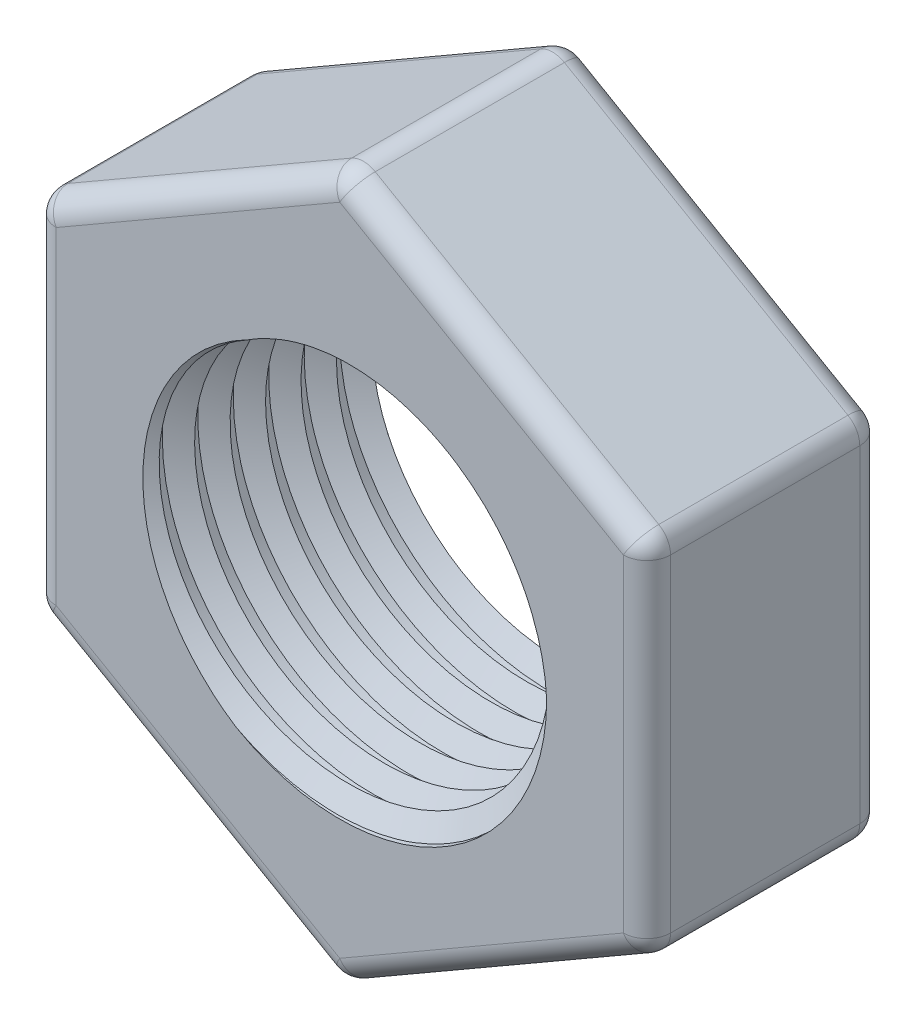
SolidWorks part; units mm, degrees
ref_plane "Front Plane" through (0, 0, 0) normal (0, 0, 1) x (1, 0, 0)
ref_plane "Top Plane" through (0, 0, 0) normal (0, 1, 0) x (1, 0, 0)
ref_plane "Right Plane" through (0, 0, 0) normal (1, 0, 0) x (0, 0, -1)
sketch "Sketch1" plane through (0, 0, 0) normal (0, 0, 1) x (1, 0, 0)
  line L1 (0, -30) -> (25.9808, -15)
  line L2 (25.9808, -15) -> (25.9808, 15)
  line L3 (25.9808, 15) -> (0, 30)
  line L4 (0, 30) -> (-25.9808, 15)
  line L5 (-25.9808, 15) -> (-25.9808, -15)
  line L6 (-25.9808, -15) -> (0, -30)
  circle A0 centre (0, 0) radius 17.5
  circle A1 centre (0, 0) radius 25.9808 construction
  dimension "D1" = 35
  dimension "D2" = 30
extrude "Boss-Extrude1" add sketch "Sketch1" along normal blind 20
sketch "Sketch2" plane through (0, 0, 0) normal (0, 0, 1) x (1, 0, 0)
  circle A0 centre (0, 0) radius 17.5
curve "Helix/Spiral1" pitch 3 height 60 radius 17.5 left hand yes centre (0, 0, 0) axis (0, 0, 1) start towards (1, 0, 0)
sketch "Sketch3" plane through (0, 0, 0) normal (0, 1, 0) x (1, 0, 0)
  line L0 (17.5, 1) -> (15.7679, 0)
  line L1 (15.7679, 0) -> (17.5, -1)
  line L2 (17.5, -1) -> (17.5, 1)
  point P3 (17.5, 0)
  dimension "D1" = 2
  dimension "D2" = 2
  dimension "D3" = 2
  dimension "D4" = 0
sweep "Sweep1" add profiles "Sketch3" path "Helix/Spiral1"
sketch "Sketch4" plane through (0, 0, 0) normal (0, 1, 0) x (1, 0, 0)
  line L1 (-25.9808, -20) -> (25.9808, -20)
  line L2 (-25.9808, -20) -> (-25.9808, -63.133)
  line L3 (-25.9808, -63.133) -> (25.9808, -63.133)
  line L4 (25.9808, -20) -> (25.9808, -63.133)
  line L5 (-25.9808, -20) -> (25.9808, -63.133) construction
  line L6 (-25.9808, -63.133) -> (25.9808, -20) construction
  point P4 (0, -41.5665)
extrude "Cut-Extrude1" cut sketch "Sketch4" against normal mid plane 80
sketch "Sketch5" plane through (0, 0, 0) normal (0, 1, 0) x (1, 0, 0)
  line L1 (25.9808, 0) -> (-25.9808, 0)
  line L2 (25.9808, 0) -> (25.9808, 6.7971)
  line L3 (25.9808, 6.7971) -> (-25.9808, 6.7971)
  line L4 (-25.9808, 0) -> (-25.9808, 6.7971)
  line L5 (25.9808, 0) -> (-25.9808, 6.7971) construction
  line L6 (25.9808, 6.7971) -> (-25.9808, 0) construction
  point P5 (0, 3.3985)
extrude "Cut-Extrude2" cut sketch "Sketch5" against normal mid plane 80
fillet "Fillet1" radius 2 18 edges at (25.9808, 0, 20) (25.9808, 0, 0) (12.9904, -22.5, 20) (25.9808, -15, 10) (12.9904, -22.5, 0) (25.9808, 15, 10) (12.9904, 22.5, 20) (12.9904, 22.5, 0) (-12.9904, -22.5, 20) (0, -30, 10) (-12.9904, -22.5, 0) (-25.9808, 0, 20) (-25.9808, -15, 10) (-25.9808, 0, 0) (0, 30, 10) (-12.9904, 22.5, 20) (-25.9808, 15, 10) (-12.9904, 22.5, 0)
